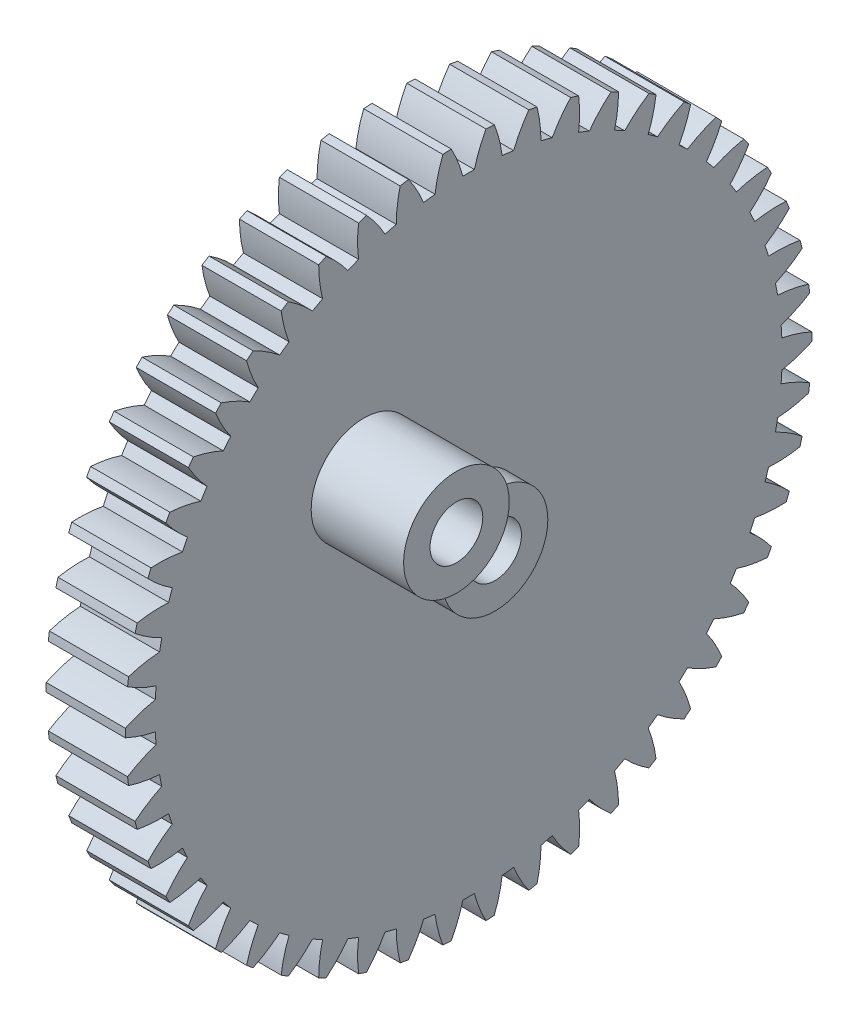
SolidWorks part; units mm, degrees
ref_plane "Plane1" through (0, 0, 0) normal (0, 0, 1) x (1, 0, 0)
ref_plane "Plane2" through (0, 0, 0) normal (0, 1, 0) x (1, 0, 0)
ref_plane "Plane3" through (0, 0, 0) normal (1, 0, 0) x (0, 0, -1)
other "Configuration Table"
sketch "HoldingSke" plane through (0, 0, 0) normal (0, 1, 0) x (1, 0, 0)
  line L0 (0, 0) -> (1.2856, -1.5321)
  line L1 (-15, 0) -> (100, 0) construction
  line L2 (0, 0) -> (-2.1039, 2.3779)
  line L3 (0, 0) -> (-11.863, 4.5341)
  line L4 (0, 0) -> (5.5511, 6.6156)
  line L5 (0, 0) -> (-46.8476, -17.4728)
  line L6 (0, 0) -> (-2.4869, -1.6779)
  line L7 (-2.1039, 2.3779) -> (8.6586, 51.2059)
  line L8 (-76.2, 54.61) -> (-75.9, 54.61)
  line L9 (-71.009, 38.7566) -> (-53.1078, 45.2721)
  line L10 (-76.2, 71.12) -> (104.1128, 71.12)
  line L11 (0, 0) -> (-3, 0)
  line L12 (-76.2, 101.6) -> (-76.181, 101.6)
  line L13 (24.9733, 27.94) -> (52.9518, 28.4284)
  line L14 (24.9733, 27.94) -> (24.9743, 27.94)
  line L15 (24.9733, 27.94) -> (100.4006, 29.5858)
  line L16 (-63.627, -0.5) -> (-12.827, -0.5)
  circle A0 centre (0, 0) radius 1
  circle A1 centre (0, 0) radius 11.874
  circle A2 centre (0, 0) radius 37.5
  circle A3 centre (0, 0) radius 1
  dimension "Num_teeth" = 50
  dimension "Pitch_radius" = 180.3128
  dimension "Width" = 3
  dimension "Thickness" = 3
sketch "BasProSke" plane through (0, 0, 0) normal (0, 1, 0) x (1, 0, 0)
  line L0 (-10, 0) -> (60, 0) construction
  line L1 (0, 0) -> (0, 13)
  line L2 (0, 0) -> (3, 0)
  line L3 (3, 0) -> (3, 13)
  line L4 (3, 13) -> (0, 13)
  dimension "Thickness" = 3
  dimension "Diameter" = 26
revolve "Base-Revolve" add sketch "BasProSke" angle 360 about L0
sketch "TooCutSke" plane through (0, 0, 0) normal (1, 0, 0) x (0, 0, -1)
  line L1 (0, 0) -> (0, 107) construction
  line L2 (0, 0) -> (-0.4259, 12.4927) construction
  line L3 (0, 0) -> (-1.5691, 24.9404) construction
  line L4 (-0.4259, 12.4927) -> (-0.7846, 12.4702) construction
  arc A0 (0.2187, 11.872) -> (-0.2187, 11.872) centre (0, 0) ccw
  arc A1 (0.6715, 13.0081) -> (-0.6715, 13.0081) centre (0, 0) ccw
  circle A2 centre (0, 0) radius 12.5 construction
  circle A3 centre (0, 0) radius 11.7462 construction
  arc A4 (-0.2187, 11.872) -> (-0.6715, 13.0081) centre (-5.0549, 10.6028) ccw
  arc A5 (0.6715, 13.0081) -> (0.2187, 11.872) centre (5.0549, 10.6028) ccw
extrude "ToothCut" cut sketch "TooCutSke" along normal through all
fillet "Breaks" [suppressed] radius 0.01 tangent propagation no
fillet "RootFillets" [suppressed] radius 0.126
pattern_circular "TeethCuts" count 50 every 7.2 about axis through (-10, 0, 0) along (1, 0, 0) of "ToothCut", "RootFillets", "Breaks"
sketch "HubNeaOneSke" plane through (0, 0, 0) normal (-1, 0, 0) x (0, 0, 1)
  circle A0 centre (0, 0) radius 11.874
  dimension "Diameter" = 23.748
extrude "HubNearOne" [suppressed] add sketch "HubNeaOneSke" along normal blind 47.0001
sketch "HubNeaBotSke" plane through (0, 0, 0) normal (-1, 0, 0) x (0, 0, 1)
  circle A0 centre (0, 0) radius 11.874
  dimension "Diameter" = 23.748
extrude "HubNearBoth" [suppressed] add sketch "HubNeaBotSke" along normal blind 23.5
ref_plane "FarPln" through (3, 0, 0) normal (1, 0, 0) x (0, 0, -1)
sketch "HubFarSke" plane through (3, 0, 0) normal (1, 0, 0) x (0, 0, -1)
  circle A0 centre (0, 0) radius 11.874
  dimension "Diameter" = 23.748
extrude "HubFar" [suppressed] add sketch "HubFarSke" along normal blind 23.5
sketch "BorSke" plane through (0, 0, 0) normal (1, 0, 0) x (0, 0, -1)
  circle A0 centre (0, 0) radius 1
  dimension "Diameter" = 2
extrude "Bore" cut sketch "BorSke" along normal mid plane 100.0001
sketch "KeySke" plane through (0, 0, 0) normal (1, 0, 0) x (0, 0, -1)
  line L0 (-0.4, 0) -> (-0.4, 1.3)
  line L1 (-0.4, 1.3) -> (0.4, 1.3)
  line L2 (0.4, 1.3) -> (0.4, 0)
  line L3 (0, 0) -> (0, 34) construction
  line L4 (-0.4, 0) -> (0.4, 0)
  dimension "Width" = 0.8
extrude "Keyway" [suppressed] cut sketch "KeySke" along normal mid plane 100.0001
pattern_circular "Keyway2" [suppressed] count 2 every 90 about axis through (-10, 0, 0) along (1, 0, 0)
sketch "草图1" plane through (3, 0, 0) normal (1, 0, 0) x (0, 0, -1)
  circle A0 centre (-3.9622, 3.8146) radius 1
  circle A1 centre (0, 0) radius 1 construction
  dimension "D1" = 5.5
extrude "切除-拉伸1" cut sketch "草图1" against normal through all
sketch "草图2" plane through (0, 0, 0) normal (-1, 0, 0) x (0, 0, 1)
  circle A0 centre (0, 0) radius 4
  circle A1 centre (0, 0) radius 1
extrude "凸台-拉伸1" add sketch "草图2" along normal blind 1.5
fillet "圆角1" radius 1.5 1 edges at (-1.5, 0, 4)
sketch "草图3" plane through (3, 0, 0) normal (1, 0, 0) x (0, 0, -1)
  circle A0 centre (-3.9622, 3.8146) radius 2
  circle A1 centre (-3.9622, 3.8146) radius 1
extrude "凸台-拉伸2" add sketch "草图3" along normal blind 3.5
sketch "草图5" plane through (3, 0, 0) normal (1, 0, 0) x (0, 0, -1)
  circle A0 centre (0, 0) radius 2
  circle A3 centre (0, 0) radius 1
extrude "凸台-拉伸3" add sketch "草图5" along normal blind 1
equation "' \"Module@HoldingSke\" = 6.35"
equation "' \"Num_teeth@HoldingSke\" = 12"
equation "' \"Ap@HoldingSke\" =  20"
equation "' \"Ap@HoldingSke\" = 20"
equation "' \"Width@HoldingSke\" = 0.5 * 25.4"
equation "' \"Hub_dia@HoldingSke\"= 1 * 25.4"
equation "' \"Hub_dia@HoldingSke\" = 1 * 25.4"
equation "' \"Overall_len@HoldingSke\" = 1.0 * 25.4"
equation "' \"Bore@HoldingSke\" = 0.75 * 25.4"
equation "' \"T_dim@HoldingSke\" = 0.1 * 25.4"
equation "' \"Width@KeySke\" = 0.25 * 25.4"
equation "' \"Show_teeth@HoldingSke\" = 13"
equation "' \"Backlash@HoldingSke\" = 0.009 * 25.4"
equation "' \"Addendum_fac@HoldingSke\" = 1.0"
equation "' \"Dedendum_fac@HoldingSke\" = 1.25"
equation "' \"Dedendum_add@HoldingSke\" = 0.00005 * 25.4"
equation "' \"Clearance_fac@HoldingSke\" = 0.25"
equation "\"Pitch@HoldingSke\" = 1 / \"Module@HoldingSke\""
equation "\"Overcut_dia@TooCutSke\" = (\"Num_teeth@HoldingSke\" + 2 * \"Addendum_fac@HoldingSke\") / \"Pitch@HoldingSke\" + 0.002 * 25.4"
equation "\"Pitch_dia@TooCutSke\" = \"Num_teeth@HoldingSke\" / \"Pitch@HoldingSke\""
equation "\"Base_dia@TooCutSke\" = \"Num_teeth@HoldingSke\" / \"Pitch@HoldingSke\" * cos((\"Ap@HoldingSke\"  * 3.14159265 / 180))"
equation "\"Root_dia@TooCutSke\" = (\"Num_teeth@HoldingSke\" + 2) / \"Pitch@HoldingSke\" - 2 * (\"Addendum_fac@HoldingSke\" + \"Dedendum_fac@HoldingSke\") / \"Pitch@HoldingSke\" - \"Dedendum_add@HoldingSke\" * 2"
equation "\"Half_ang@TooCutSke\" = 180 / \"Num_teeth@HoldingSke\""
equation "\"Half_CT@TooCutSke\" = \"Num_teeth@HoldingSke\" / \"Pitch@HoldingSke\" * sin((3.14159265 / 2 / \"Num_teeth@HoldingSke\")) / 2 - 7 * \"Backlash@HoldingSke\" / 4"
equation "\"Flank_rad@TooCutSke\" = \"Num_teeth@HoldingSke\" / \"Pitch@HoldingSke\" / 5"
equation "\"Radius@RootFillets\" = \"Clearance_fac@HoldingSke\" / \"Pitch@HoldingSke\" + \"Dedendum_add@HoldingSke\""
equation "\"Break_rad@Breaks\" = 0.02 / \"Pitch@HoldingSke\""
equation "\"Thickness@HoldingSke\" = \"Width@HoldingSke\""
equation "\"OAL@HoldingSke\" = \"Thickness@HoldingSke\""
equation "\"MHD@HoldingSke\" = (\"Num_teeth@HoldingSke\" + 2) / \"Pitch@HoldingSke\" - 2 * (\"Addendum_fac@HoldingSke\" + \"Dedendum_fac@HoldingSke\")  / \"Pitch@HoldingSke\" - \"Dedendum_add@HoldingSke\" * 2"
equation "\"MBD@HoldingSke\" = (\"Num_teeth@HoldingSke\" + 2) / \"Pitch@HoldingSke\" - 2 * (\"Addendum_fac@HoldingSke\" + \"Dedendum_fac@HoldingSke\")  / \"Pitch@HoldingSke\" - \"Dedendum_add@HoldingSke\" * 2 - 0.002 * 25.4"
equation "\"MHD@HoldingSke\" = ((sgn( \"MHD@HoldingSke\" - \"Hub_dia@HoldingSke\" )-1)*( \"MHD@HoldingSke\" - \"Hub_dia@HoldingSke\" ))/-2+ \"Hub_dia@HoldingSke\""
equation "\"MBD@HoldingSke\" = ((sgn( \"MBD@HoldingSke\" - \"Bore@HoldingSke\" )-1)*( \"MBD@HoldingSke\" - \"Bore@HoldingSke\" ))/-2+ \"Bore@HoldingSke\""
equation "\"OAL@HoldingSke\" = ((sgn( \"OAL@HoldingSke\" - \"Overall_len@HoldingSke\" )+1)*( \"OAL@HoldingSke\" - \"Overall_len@HoldingSke\" ))/2 + \"Overall_len@HoldingSke\" + 0.000002 * 25.4"
equation "\"Num_teeth@TeethCuts\" = int( \"Show_teeth@HoldingSke\" ) + 1"
equation "\"Num_teeth@TeethCuts\" = ((sgn( \"Num_teeth@TeethCuts\" - \"Num_teeth@HoldingSke\" )-1)*( \"Num_teeth@TeethCuts\" - \"Num_teeth@HoldingSke\" ))/-2+ \"Num_teeth@HoldingSke\""
equation "\"Num_teeth@TeethCuts\" = ((sgn( \"Num_teeth@TeethCuts\" - 2.0)+1)*( \"Num_teeth@TeethCuts\" - 2.0))/2 +2.0"
equation "\"Angle@TeethCuts\" = 360.0 / \"Num_teeth@HoldingSke\""
equation "\"Diameter@BasProSke\" = (\"Num_teeth@HoldingSke\" + 2 * \"Addendum_fac@HoldingSke\") / \"Pitch@HoldingSke\""
equation "\"Thickness@BasProSke\"  = \"Thickness@HoldingSke\""
equation "' \"Fillet_rad@BasProSke\" =  \"Thickness@HoldingSke\" * 0.05"
equation "' \"Fillet_rad@BasProSke\" = \"Thickness@HoldingSke\" * 0.05"
equation "\"MHD@HoldingSke\" = ((sgn( \"MHD@HoldingSke\" - \"Root_dia@TooCutSke\" )-1)*( \"MHD@HoldingSke\" - \"Root_dia@TooCutSke\" ))/-2+ \"Root_dia@TooCutSke\""
equation "\"Diameter@HubNeaOneSke\" = \"MHD@HoldingSke\""
equation "\"Length@HubNearOne\" = \"OAL@HoldingSke\" - \"Thickness@BasProSke\""
equation "\"Diameter@HubNeaBotSke\" = \"MHD@HoldingSke\""
equation "\"Length@HubNearBoth\" = ( \"OAL@HoldingSke\" - \"Thickness@BasProSke\" ) / 2.0"
equation "\"Thickness@FarPln\" = \"Thickness@BasProSke\""
equation "\"Diameter@HubFarSke\" = \"MHD@HoldingSke\""
equation "\"Length@HubFar\" = ( \"OAL@HoldingSke\" - \"Thickness@BasProSke\" ) / 2.0"
equation "\"Diameter@BorSke\" = \"MBD@HoldingSke\""
equation "\"D1@Bore\" = \"OAL@HoldingSke\" * 2.0"
equation "\"D1@Keyway\" = \"OAL@HoldingSke\" * 2.0"
equation "\"Offset@KeySke\" = \"T_dim@HoldingSke\" + \"MBD@HoldingSke\" / 2.0"
